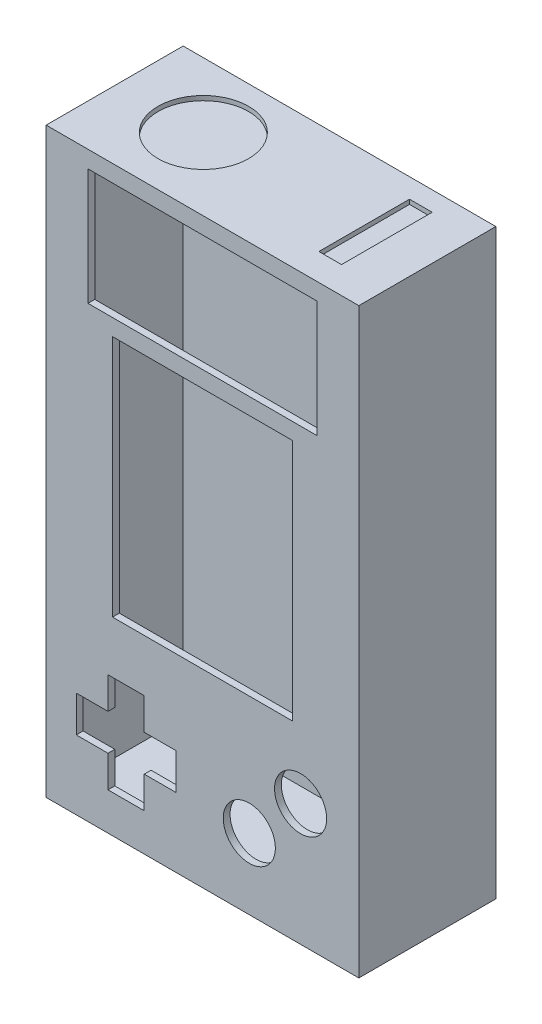
SolidWorks part; units mm, degrees
note: The reader was unsure of these and kept them because the rebuilt part matched: shared geometry of "Sketch1<3>", "Sketch1<4>", "Sketch1<5>", "Sketch1<6>".
ref_plane "Front Plane" through (0, 0, 0) normal (0, 0, 1) x (1, 0, 0)
ref_plane "Top Plane" through (0, 0, 0) normal (0, 1, 0) x (1, 0, 0)
ref_plane "Right Plane" through (0, 0, 0) normal (1, 0, 0) x (0, 0, -1)
sketch "Sketch1" plane through (0, 0, 0) normal (0, 0, 1) x (1, 0, 0)
  line L0 (-4, -4) -> (-11, -4)
  line L1 (49.8546, 107.7175) -> (-16.1454, 107.7175)
  line L2 (49.8546, 107.7175) -> (49.8546, -17.7825)
  line L3 (49.8546, -17.7825) -> (-16.1454, -17.7825)
  line L4 (-16.1454, 107.7175) -> (-16.1454, -17.7825)
  line L5 (16.8546, -17.7825) -> (16.8546, 107.7175) construction
  line L6 (49.8546, 44.9675) -> (-16.1454, 44.9675) construction
  line L7 (-11, -4) -> (-11, 4)
  line L8 (-11, 4) -> (-4, 4)
  line L9 (-4, 4) -> (-4, 11)
  line L10 (-4, 11) -> (4, 11)
  line L11 (4, 11) -> (4, 4)
  line L12 (4, 4) -> (11, 4)
  line L13 (11, 4) -> (11, -4)
  line L14 (11, -4) -> (4, -4)
  line L15 (4, -4) -> (4, -11)
  line L16 (4, -11) -> (-4, -11)
  line L17 (-4, -11) -> (-4, -4)
  line L18 (-3.5, 10.3) -> (-3.5, 3.7) construction
  line L19 (3.5, 3.7) -> (3.5, 10.3) construction
  line L20 (3.3, 10.5) -> (-3.3, 10.5) construction
  line L21 (-3.3, -10.5) -> (3.3, -10.5) construction
  line L22 (-2.0054, 75.1221) -> (-2.0054, 76.1221) construction
  line L23 (36.7146, 76.1221) -> (-3.0054, 76.1221)
  line L24 (36.7146, 76.1221) -> (36.7146, 22.5121)
  line L25 (36.7146, 22.5121) -> (-3.0054, 22.5121)
  line L26 (-3.0054, 76.1221) -> (-3.0054, 22.5121)
  line L27 (16.8546, 22.5121) -> (16.8546, 76.1221) construction
  line L28 (36.7146, 49.3171) -> (-3.0054, 49.3171) construction
  line L29 (42.1296, 105.4705) -> (-8.4204, 105.4705)
  line L30 (42.1296, 105.4705) -> (42.1296, 79.7655)
  line L31 (42.1296, 79.7655) -> (-8.4204, 79.7655)
  line L32 (-8.4204, 105.4705) -> (-8.4204, 79.7655)
  line L33 (16.8546, 79.7655) -> (16.8546, 105.4705) construction
  line L34 (42.1296, 92.618) -> (-8.4204, 92.618) construction
  line L35 (-2.0054, 75.1221) -> (-3.0054, 75.1221) construction
  line L36 (35.7146, 23.5121) -> (36.7146, 23.5121) construction
  line L37 (35.7146, 23.5121) -> (35.7146, 22.5121) construction
  line L38 (-7.4204, 80.7655) -> (-7.4204, 79.7655) construction
  line L39 (-7.4204, 80.7655) -> (-8.4204, 80.7655) construction
  line L40 (41.1296, 104.4705) -> (41.1296, 105.4705) construction
  line L41 (41.1296, 104.4705) -> (42.1296, 104.4705) construction
  line L42 (-15.6454, 85.7175) -> (-16.1454, 85.7175) construction
  line L43 (49.3546, -17.2825) -> (49.3546, -17.7825) construction
  line L44 (-10.8954, 107.2175) -> (-10.8954, 107.7175) construction
  line L45 (-3.0054, 22.5121) -> (-3.0054, 21.0121) construction
  line L46 (49.3546, -17.2825) -> (49.8546, -17.2825) construction
  line L47 (38.2146, 77.6221) -> (-4.5054, 77.6221)
  line L48 (38.2146, 77.6221) -> (38.2146, 21.0121)
  line L49 (38.2146, 21.0121) -> (-4.5054, 21.0121)
  line L50 (-4.5054, 77.6221) -> (-4.5054, 21.0121)
  line L51 (38.2146, 77.6221) -> (-4.5054, 21.0121) construction
  line L52 (38.2146, 21.0121) -> (-4.5054, 77.6221) construction
  line L53 (-9.9204, 106.9705) -> (43.6296, 106.9705)
  line L54 (-9.9204, 106.9705) -> (-9.9204, 78.2655)
  line L55 (-9.9204, 78.2655) -> (43.6296, 78.2655)
  line L56 (43.6296, 106.9705) -> (43.6296, 78.2655)
  line L57 (-9.9204, 106.9705) -> (43.6296, 78.2655) construction
  line L58 (-9.9204, 78.2655) -> (43.6296, 106.9705) construction
  line L59 (-3.0054, 22.5121) -> (-4.5054, 22.5121) construction
  line L60 (-8.4204, 79.7655) -> (-8.4204, 78.2655) construction
  line L61 (-8.4204, 79.7655) -> (-9.9204, 79.7655) construction
  line L62 (49.8546, -17.7825) -> (49.8546, -19.2825) construction
  line L63 (-17.6454, 109.2175) -> (51.3546, 109.2175)
  line L64 (-17.6454, 109.2175) -> (-17.6454, -19.2825)
  line L65 (-17.6454, -19.2825) -> (51.3546, -19.2825)
  line L66 (51.3546, 109.2175) -> (51.3546, -19.2825)
  line L67 (-17.6454, 109.2175) -> (51.3546, -19.2825) construction
  line L68 (-17.6454, -19.2825) -> (51.3546, 109.2175) construction
  line L69 (49.8546, -17.7825) -> (51.3546, -17.7825) construction
  circle A0 centre (27.1865, -3.6948) radius 5.75
  circle A1 centre (38.5002, 7.6189) radius 5.75
  arc A2 (22.4284, -5.9135) -> (29.4053, -8.4529) centre (27.1865, -3.6948) ccw construction
  arc A3 (27.5218, -3.5384) -> (26.8512, -3.8511) centre (27.1865, -3.6948) ccw construction
  arc A4 (38.8355, 7.7753) -> (38.1649, 7.4626) centre (38.5002, 7.6189) ccw construction
  point P0 (16.8546, 44.9675)
  point P31 (16.8546, 92.618)
  point P39 (16.8546, 49.3171)
  point P59 (16.8546, 49.3171)
  point P68 (16.8546, 92.618)
  point P79 (16.8546, 44.9675)
  dimension "D5" = 0.5
  dimension "D1" = 0.5
  dimension "D2" = 0.5
  dimension "D3" = 0.5
  dimension "D4" = 0.5
  dimension "D6" = 1
  dimension "D7" = 1
  dimension "D8" = 0.5
  dimension "D9" = 1.5
  dimension "D10" = 1.5
  dimension "D11" = 1.5
extrude "Boss-Extrude1" add sketch "Sketch1" along normal blind 1.5 contours L1 L4 L3 L2 A1 A0 L32 L29 L30 L31 L26 L23 L24 L25 L16 L17 L0 L7 L8 L9 L10 L11 L12 L13 L14 L15 | L47 L50 L49 L48 L26 L23 L24 L25 | L56 L53 L54 L55 L32 L29 L30 L31
extrude "Boss-Extrude2" add sketch "Sketch1<3>" against normal up to surface (0.0005 mm away) contours L47 L50 L49 L48 L26 L23 L24 L25
sketch "Sketch1<3>" plane through (0, 0, 0) normal (0, 0, 1) x (1, 0, 0) same geometry as "Sketch1"
extrude "Boss-Extrude3" add sketch "Sketch1<4>" against normal up to surface (0.0005 mm away) contours L56 L53 L54 L55 L32 L29 L30 L31
sketch "Sketch1<4>" plane through (0, 0, 0) normal (0, 0, 1) x (1, 0, 0) same geometry as "Sketch1"
extrude "Boss-Extrude4" add sketch "Sketch1<5>" along normal up to surface and the other way up to surface contours L66 L63 L64 L65 L4 L1 L2 L3
sketch "Sketch1<5>" plane through (0, 0, 0) normal (0, 0, 1) x (1, 0, 0) same geometry as "Sketch1"
extrude "Boss-Extrude5" add sketch "Sketch1<6>" against normal blind 1.5 from surface at -27.2345 contours L64 L65 L66 L63 starting at face at (16.8546, 44.9675, -27.2345)
sketch "Sketch1<6>" plane through (0, 0, 0) normal (0, 0, 1) x (1, 0, 0) same geometry as "Sketch1"
sketch "Sketch2" plane through (0, 109.2175, 0) normal (0, 1, 0) x (1, 0, 0)
  line L0 (36.6046, 24.4345) -> (36.6046, 4.4345) construction
  line L1 (36.6046, 4.4345) -> (41.6046, 4.4345)
  line L2 (36.6046, 4.4345) -> (36.6046, 24.4345)
  line L3 (36.6046, 24.4345) -> (41.6046, 24.4345)
  line L4 (41.6046, 4.4345) -> (41.6046, 24.4345)
  line L5 (36.6046, 4.4345) -> (41.6046, 4.4345) construction
  circle A0 centre (1.1046, 14.4345) radius 10
  circle A1 centre (1.1046, 14.4345) radius 10 construction
extrude "Cut-Extrude1" cut sketch "Sketch2" against normal blind 1
